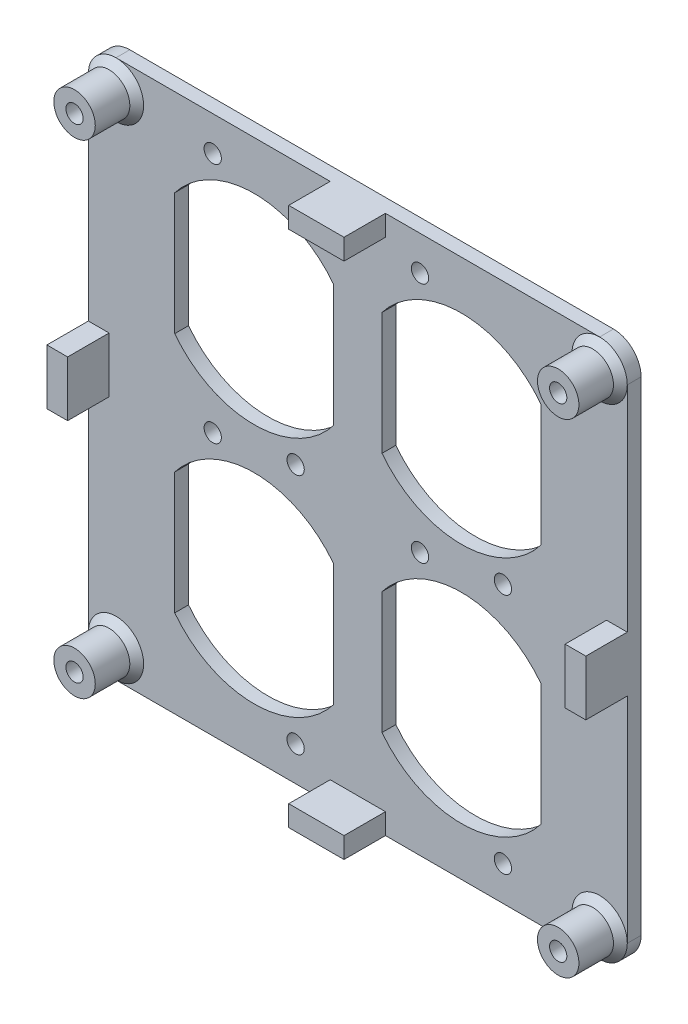
SolidWorks part; units mm, degrees
ref_plane "Front Plane" through (0, 0, 0) normal (0, 0, 1) x (1, 0, 0)
ref_plane "Top Plane" through (0, 0, 0) normal (0, 1, 0) x (1, 0, 0)
ref_plane "Right Plane" through (0, 0, 0) normal (1, 0, 0) x (0, 0, -1)
sketch "Sketch1" plane through (0, 0, 0) normal (0, 0, 1) x (1, 0, 0)
  line L1 (-39, -39) -> (39, -39)
  line L2 (-39, -39) -> (-39, 39)
  line L3 (-39, 39) -> (39, 39)
  line L4 (39, -39) -> (39, 39)
  line L5 (-39, -39) -> (39, 39) construction
  line L6 (-39, 39) -> (39, -39) construction
  point P0 (0, 0)
  dimension "D1" = 78
  dimension "D2" = 78
extrude "Boss-Extrude1" add sketch "Sketch1" along normal blind 2
sketch "Sketch2" plane through (0, 0, 2) normal (0, 0, 1) x (1, 0, 0)
  line L2 (-26.5, 8.6682) -> (-26.5, 26.3318)
  line L4 (-3.5, 8.6682) -> (-3.5, 26.3318)
  line L5 (-26.5, 8.6682) -> (-3.5, 26.3318) construction
  line L6 (-26.5, 26.3318) -> (-3.5, 8.6682) construction
  arc A0 (-26.5, 26.3318) -> (-3.5, 26.3318) centre (-15, 17.5) cw
  arc A1 (-26.5, 8.6682) -> (-3.5, 8.6682) centre (-15, 17.5) ccw
  point P0 (-15, 17.5)
  point P7 (-15, 3)
  point P9 (-15, 32)
  dimension "D1" = 23
  dimension "D2" = 17.5
  dimension "D3" = 15
  dimension "D4" = 29
extrude "Cut-Extrude1" cut sketch "Sketch2" against normal through all
sketch "Sketch3" plane through (0, 0, 2) normal (0, 0, 1) x (1, 0, 0)
  line L0 (-15, 32) -> (-15, 3) construction
  circle A0 centre (-21, 34) radius 1.25
  circle A1 centre (-9, 1) radius 1.25
  arc A2 (-3.5, 26.3318) -> (-26.5, 26.3318) centre (-15, 17.5) ccw construction
  arc A3 (-26.5, 8.6682) -> (-3.5, 8.6682) centre (-15, 17.5) ccw construction
  point P12 (-15, 17.5)
  dimension "D3" = 2.5
  dimension "D1" = 6
  dimension "D2" = 6
  dimension "D4" = 16.5
  dimension "D5" = 16.5
extrude "Cut-Extrude6" cut sketch "Sketch3" against normal through all
pattern_linear "LPattern1" count 2 spacing 35 along (0, -1, 0) count 2 spacing 30 along (1, 0, 0) of "Cut-Extrude1", "Cut-Extrude6"
fillet "Fillet1" radius 4 4 edges at (39, -39, 1) (39, 39, 1) (-39, 39, 1) (-39, -39, 1)
sketch "Sketch25" plane through (0, 0, 2) normal (0, 0, 1) x (1, 0, 0)
  line L0 (-39, 35) -> (-39, -35) construction
  line L1 (35, 39) -> (-35, 39) construction
  circle A0 centre (-35, 35) radius 3
  dimension "D1" = 6
  dimension "D2" = 4
  dimension "D3" = 4
extrude "Boss-Extrude4" add sketch "Sketch25" along normal blind 6
sketch "Sketch26" plane through (0, 0, 8) normal (0, 0, 1) x (1, 0, 0)
  circle A0 centre (-35, 35) radius 1.25
  dimension "D1" = 2.5
extrude "Cut-Extrude9" cut sketch "Sketch26" against normal blind 3
mirror "Mirror2" about plane through (0, 0, 0) normal (1, 0, 0) of "Cut-Extrude9", "Boss-Extrude4"
mirror "Mirror3" about plane through (0, 0, 0) normal (0, 1, 0) of "Mirror2"
chamfer "Chamfer1" distance 1 distance2 1 4 edges at (32, -35, 2) (-32, -35, 2) (-38, 35, 2) (32, 35, 2)
sketch "Sketch27" plane through (0, 0, 0) normal (0, 0, 1) x (1, 0, 0)
  line L0 (39, -35) -> (39, 35) construction
  line L1 (39, -4) -> (36, -4)
  line L2 (39, -4) -> (39, 4)
  line L3 (39, 4) -> (36, 4)
  line L4 (36, -4) -> (36, 4)
  line L5 (0, 0) -> (39, 0) construction
  dimension "D1" = 8
  dimension "3" = 3
extrude "Boss-Extrude5" add sketch "Sketch27" along normal up to surface (8 mm away) up to face at (32, 35, 8)
ref_axis "Axis1" through (0, 0, 8.4) along (0, 0, -1)
pattern_circular "CirPattern1" count 4 over 360 about axis through (0, 0, 8.4) along (0, 0, -1) of "Boss-Extrude5"
equation "\"`3\"=10"
